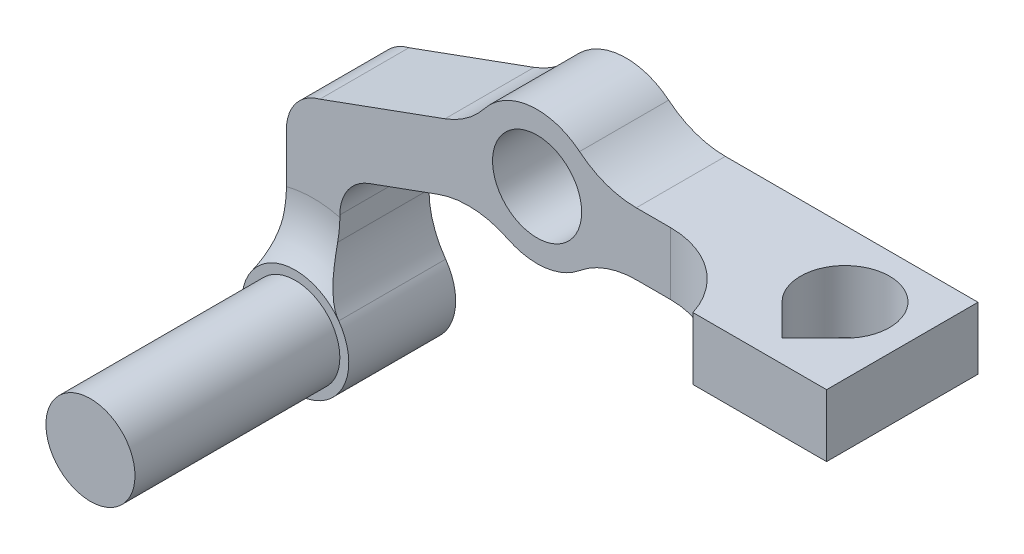
SolidWorks part; units mm, degrees
ref_plane "Alzado" through (0, 0, 0) normal (0, 0, 1) x (1, 0, 0)
ref_plane "Planta" through (0, 0, 0) normal (0, 1, 0) x (1, 0, 0)
ref_plane "Vista lateral" through (0, 0, 0) normal (1, 0, 0) x (0, 0, -1)
sketch "Croquis1" plane through (0, 0, 0) normal (0, 0, 1) x (1, 0, 0)
  circle A0 centre (0, 0) radius 5
  circle A1 centre (0, 0) radius 7.5
  dimension "D1" = 10
  dimension "D2" = 15
extrude "Saliente-Extruir1" add sketch "Croquis1" along normal mid plane 10
sketch3d "Croquis3D1"
  line L0 (0, 0, 0) -> (-4, 0, 0) construction
  line L1 (0, 0, 0) -> (4, 0, 0) construction
  line L2 (-4, 0, 0) -> (-25.1431, -7.6955, 0) construction
  line L3 (-4, 0, 0) -> (-25.1431, 0, 0) construction
  line L4 (-25.1431, 0, 0) -> (-25.1431, -7.6955, 0) construction
  line L5 (4, 0, 0) -> (31.8935, 0, 2.4404) construction
  line L6 (31.8935, 0, 2.4404) -> (4, 0, 2.4404) construction
  line L7 (4, 0, 2.4404) -> (4, 0, 0) construction
  line L8 (4, 0, 2.4404) -> (32, 0, 2.4404) construction
  line L9 (32, 0, 2.4404) -> (32, 0, 0) construction
  line L10 (32, 0, 0) -> (4, 0, 0) construction
  dimension "D1" = 4
  dimension "D2" = 4
  dimension "D3" = 22.5
  dimension "D4" = 20
  dimension "D5" = 85
  dimension "D6" = 28
  dimension "D7" = 28
ref_plane "Plano1" through (-25.1431, -7.6955, 0) normal (-0.9397, -0.342, 0) x (0, 0, 1)
sketch "Croquis23" plane through (-25.1431, -7.6955, 0) normal (-0.9397, -0.342, 0) x (0, 0, 1)
  line L1 (-5, 3.5) -> (5, 3.5)
  line L2 (-5, 3.5) -> (-5, -3.5)
  line L3 (-5, -3.5) -> (5, -3.5)
  line L4 (5, 3.5) -> (5, -3.5)
  line L5 (-5, 3.5) -> (5, -3.5) construction
  line L6 (-5, -3.5) -> (5, 3.5) construction
  point P0 (0, 0)
  dimension "D1" = 7
  dimension "D2" = 10
extrude "Saliente-Extruir15" add sketch "Croquis23" against normal blind 21
ref_plane "Plano2" through (32, 0, 0) normal (1, 0, 0) x (0, 0, -1)
sketch "Croquis3" plane through (32, 0, 0) normal (1, 0, 0) x (0, 0, -1)
  line L1 (-5, 3.5) -> (5, 3.5)
  line L2 (-5, 3.5) -> (-5, -3.5)
  line L3 (-5, -3.5) -> (5, -3.5)
  line L4 (5, 3.5) -> (5, -3.5)
  line L5 (-5, 3.5) -> (5, -3.5) construction
  line L6 (-5, -3.5) -> (5, 3.5) construction
  point P0 (0, 0)
  dimension "D1" = 10
  dimension "D2" = 7
extrude "Saliente-Extruir3" add sketch "Croquis3" against normal up to surface (25.3668 mm away) up to face at (0.4498, 0.0634, 0)
ref_plane "Plano3" through (-25.1431, -7.6955, 0) normal (0, 1, 0) x (1, 0, 0)
sketch "Croquis7" plane through (-25.1431, -7.6955, 0) normal (0, 1, 0) x (1, 0, 0)
  line L1 (-3, -5) -> (3, -5)
  line L2 (-3, -5) -> (-3, 5)
  line L3 (-3, 5) -> (3, 5)
  line L4 (3, -5) -> (3, 5)
  line L5 (-3, -5) -> (3, 5) construction
  line L6 (-3, 5) -> (3, -5) construction
  point P0 (0, 0)
  dimension "D1" = 6
  dimension "D2" = 10
extrude "Saliente-Extruir7" add sketch "Croquis7" along normal mid plane 8
sketch "Croquis20" plane through (0, 0, -5) normal (0, 0, -1) x (-1, 0, 0)
  line L1 (-39.5, 3.5) -> (-24.5, 3.5)
  line L2 (-39.5, 3.5) -> (-39.5, -3.5)
  line L3 (-39.5, -3.5) -> (-24.5, -3.5)
  line L4 (-24.5, 3.5) -> (-24.5, -3.5)
  line L5 (-39.5, 3.5) -> (-24.5, -3.5) construction
  line L6 (-39.5, -3.5) -> (-24.5, 3.5) construction
  point P0 (-32, 0)
  dimension "D1" = 7
  dimension "D2" = 15
extrude "Saliente-Extruir13" add sketch "Croquis20" against normal blind 17
sketch "Croquis21" plane through (0, -3.5, 0) normal (0, -1, 0) x (1, 0, 0)
  line L0 (32, 9.5) -> (28.4645, 5.9645)
  line L1 (32, 9.5) -> (35.5355, 5.9645)
  line L2 (32, 2.4289) -> (32, 9.5) construction
  line L3 (32, 12) -> (32, 9.5) construction
  line L4 (39.5, 12) -> (24.5, 12) construction
  arc A0 (28.4645, 5.9645) -> (35.5355, 5.9645) centre (32, 2.4289) ccw
  point P5 (0, 0)
  dimension "D1" = 10
  dimension "D2" = 90
  dimension "D3" = 2.5
extrude "Cortar-Extruir3" cut sketch "Croquis21" against normal through all
ref_plane "Plano4" through (-25.1431, 0, 0) normal (1, 0, 0) x (0, 0, -1)
sketch "Croquis8" plane through (-25.1431, 0, 0) normal (1, 0, 0) x (0, 0, -1)
  line L0 (5, -11.6955) -> (5, -17.6955)
  line L4 (-5, -17.6955) -> (-5, -11.6955)
  line L5 (-5, -11.6955) -> (5, -11.6955)
  line L7 (-5, -26.6955) -> (-5, -17.6955)
  line L8 (5, -17.6955) -> (5, -26.6955)
  line L11 (5, -26.6955) -> (-5, -26.6955)
  dimension "D1" = 15
  dimension "D2" = 6
extrude "Saliente-Extruir8" add sketch "Croquis8" along normal mid plane 6
sketch "Croquis9" plane through (0, 0, 5) normal (0, 0, 1) x (1, 0, 0)
  line L0 (-25.1431, -17.6955) -> (-25.1431, -25.6955) construction
  line L2 (-25.1431, -25.6955) -> (-25.1431, -28.6955) construction
  circle A0 centre (-25.1431, -25.6955) radius 6
  dimension "D2" = 12
  dimension "D1" = 3
extrude "Saliente-Extruir9" add sketch "Croquis9" against normal blind 10 and the other way blind 2
sketch "Croquis24" plane through (0, 0, 7) normal (0, 0, 1) x (1, 0, 0)
  circle A0 centre (-25.1431, -25.6955) radius 5
  dimension "D1" = 10
extrude "Saliente-Extruir16" add sketch "Croquis24" along normal blind 23
fillet "Redondeo2" radius 10 8 edges at (-25.1431, -19.6955, 5) (-28.1431, -20.4993, 0) (-22.1431, -20.4993, 0) (24.5, 0, 5) (-6.0278, -4.4627, 0) (6.6332, -3.5, 0) (6.6332, 3.5, 0) (-7.0263, 2.6231, 0)
fillet "Redondeo3" radius 5 1 edges at (-22.1431, -10.3282, 0)
fillet "Redondeo4" radius 5 1 edges at (-28.1431, -3.6955, 0)
